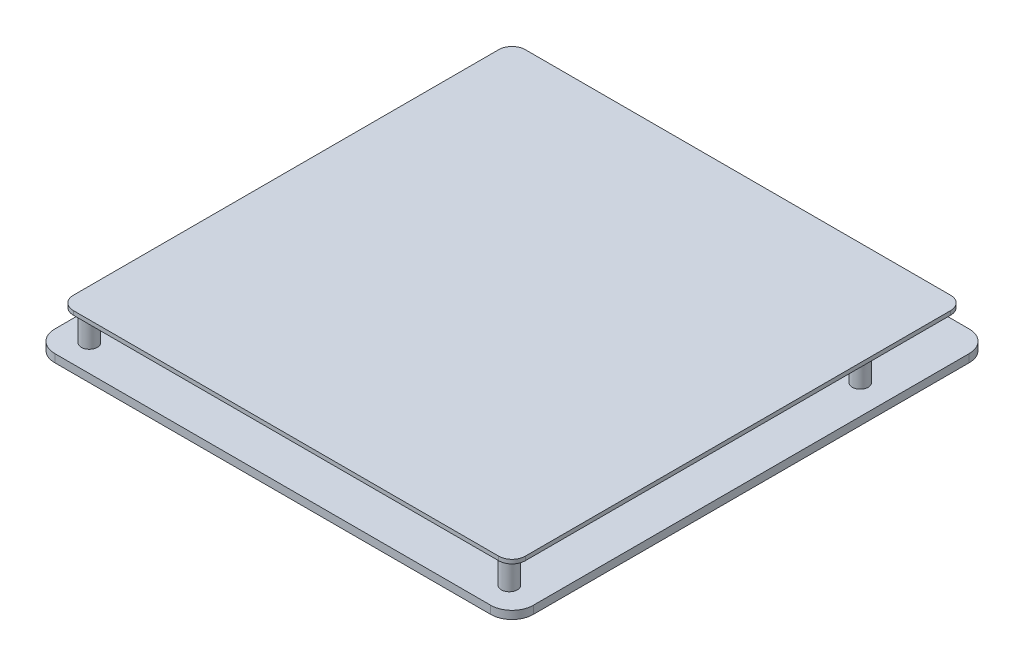
SolidWorks part; units mm, degrees
ref_plane "Plano frontal" through (0, 0, 0) normal (0, 0, 1) x (1, 0, 0)
ref_plane "Plano superior" through (0, 0, 0) normal (0, 1, 0) x (1, 0, 0)
ref_plane "Plano direito" through (0, 0, 0) normal (1, 0, 0) x (0, 0, -1)
sketch "Esboço1" plane through (0, 0, 0) normal (0, 1, 0) x (1, 0, 0)
  line L1 (82, -90) -> (-82, -90)
  line L2 (90, -82) -> (90, 82)
  line L3 (82, 90) -> (-82, 90)
  line L4 (-90, -82) -> (-90, 82)
  line L5 (90, -90) -> (-90, 90) construction
  line L6 (90, 90) -> (-90, -90) construction
  arc A0 (82, -90) -> (90, -82) centre (82, -82) ccw
  arc A1 (-82, -90) -> (-90, -82) centre (-82, -82) cw
  arc A2 (90, 82) -> (82, 90) centre (82, 82) ccw
  arc A3 (-82, 90) -> (-90, 82) centre (-82, 82) ccw
  point P0 (0, 0)
  dimension "D3" = 8
  dimension "D1" = 180
  dimension "D2" = 180
extrude "Ressalto-extrusão1" add sketch "Esboço1" along normal blind 3
sketch "Esboço2" plane through (0, 0, 0) normal (0, -1, 0) x (-1, 0, 0)
  line L0 (82, -90) -> (-82, -90) construction
  line L1 (90, 82) -> (90, -82) construction
  line L2 (0, 0) -> (-90, 0) construction
  line L3 (-90, -82) -> (-90, 82) construction
  line L4 (0, 0) -> (0, -90) construction
  circle A0 centre (79, -62) radius 3.5
  circle A1 centre (-79, -62) radius 3.5
  circle A2 centre (-79, 62) radius 3.5
  circle A3 centre (79, 62) radius 3.5
  dimension "D1" = 7
  dimension "D2" = 28
  dimension "D3" = 11
extrude "Ressalto-extrusão2" add sketch "Esboço2" along normal blind 5
sketch "Esboço3" plane through (0, 3, 0) normal (0, 1, 0) x (1, 0, 0)
  line L0 (90, -82) -> (90, 82) construction
  line L1 (-82, -90) -> (82, -90) construction
  line L2 (-90, 82) -> (-90, -82) construction
  line L3 (82, 90) -> (-82, 90) construction
  circle A0 centre (-79, -80) radius 3
  circle A1 centre (-79, 75) radius 3
  circle A2 centre (79, 52) radius 3
  circle A3 centre (79, -80) radius 3
  point P13 (0, 0)
  point P14 (0, 0)
  dimension "D1" = 6
  dimension "D3" = 11
  dimension "D5" = 10
  dimension "D6" = 38
  dimension "D2" = 10
  dimension "D4" = 11
  dimension "D7" = 15
extrude "Ressalto-extrusão3" add sketch "Esboço3" along normal blind 11
sketch "Esboço4" plane through (0, 14, 0) normal (0, 1, 0) x (1, 0, 0)
  line L1 (-80, 85) -> (80, 85)
  line L2 (-85, 80) -> (-85, -80)
  line L3 (-80, -85) -> (80, -85)
  line L4 (85, 80) -> (85, -80)
  line L5 (-85, 85) -> (85, -85) construction
  line L6 (-85, -85) -> (85, 85) construction
  arc A1 (80, -85) -> (85, -80) centre (80, -80) ccw
  arc A2 (-85, -80) -> (-80, -85) centre (-80, -80) ccw
  arc A3 (80, 85) -> (85, 80) centre (80, 80) cw
  arc A4 (-80, 85) -> (-85, 80) centre (-80, 80) ccw
  point P0 (0, 0)
  point P8 (0, 0)
  dimension "D3" = 5
  dimension "D1" = 170
  dimension "D2" = 170
extrude "Ressalto-extrusão4" add sketch "Esboço4" along normal blind 1.5
